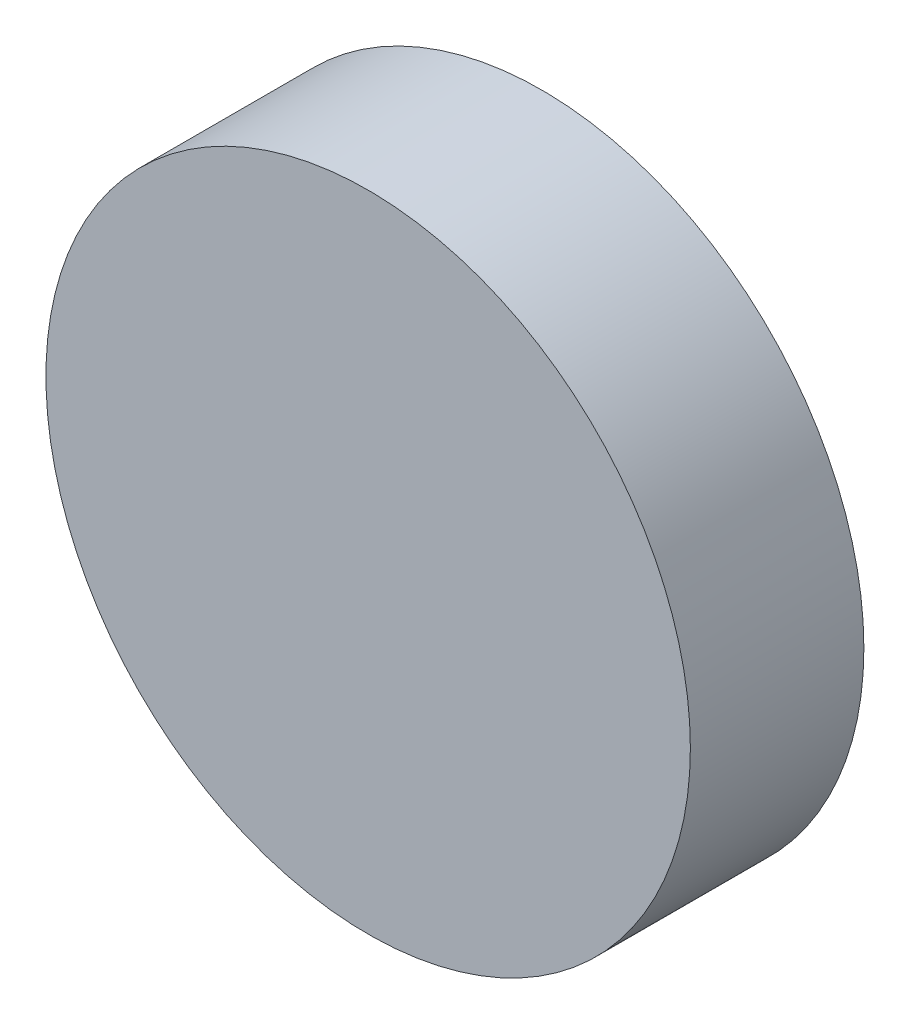
SolidWorks part; units mm, degrees
ref_plane "Front Plane" through (0, 0, 0) normal (0, 0, 1) x (1, 0, 0)
ref_plane "Top Plane" through (0, 0, 0) normal (0, 1, 0) x (1, 0, 0)
ref_plane "Right Plane" through (0, 0, 0) normal (1, 0, 0) x (0, 0, -1)
sketch "Sketch1" plane through (0, 0, 0) normal (0, 0, 1) x (1, 0, 0)
  circle A0 centre (0, 0) radius 6.5
  dimension "D1" = 13
extrude "Boss-Extrude1" add sketch "Sketch1" along normal blind 3.5
